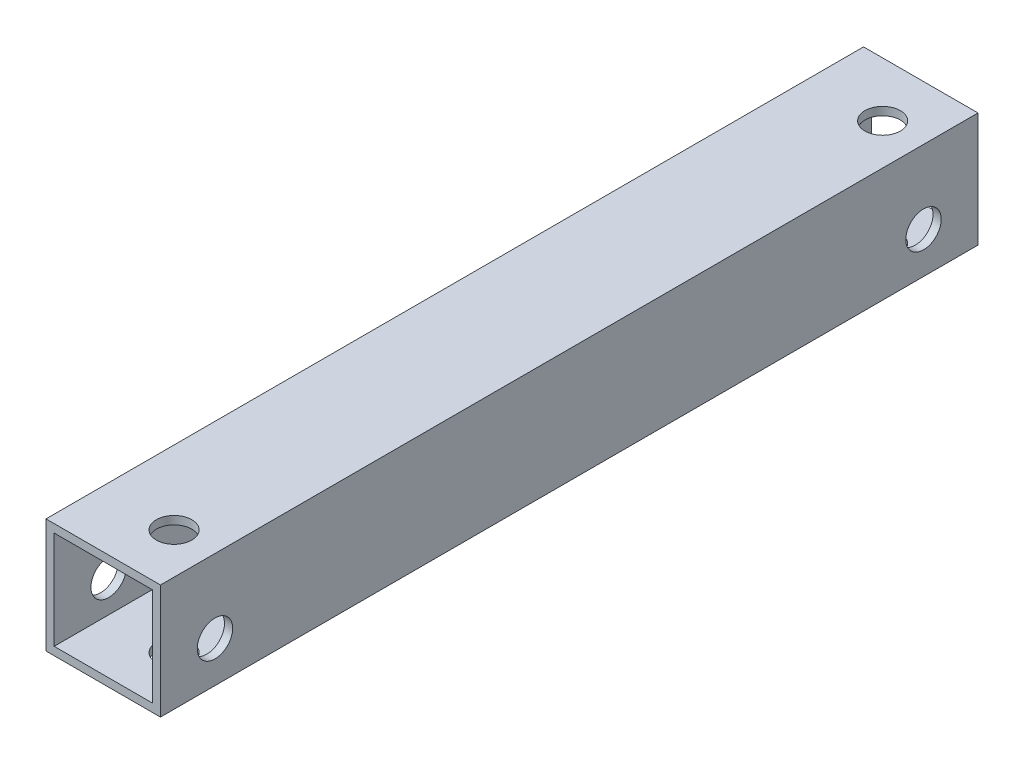
SolidWorks part; units mm, degrees
ref_plane "Alzado" through (0, 0, 0) normal (0, 0, 1) x (1, 0, 0)
ref_plane "Planta" through (0, 0, 0) normal (0, 1, 0) x (1, 0, 0)
ref_plane "Vista lateral" through (0, 0, 0) normal (1, 0, 0) x (0, 0, -1)
sketch "Croquis1" plane through (0, 0, 0) normal (0, 0, 1) x (1, 0, 0)
  line L0 (-18, 18) -> (18, 18)
  line L1 (-21, -21) -> (21, -21)
  line L2 (-21, -21) -> (-21, 21)
  line L3 (-21, 21) -> (21, 21)
  line L4 (21, -21) -> (21, 21)
  line L5 (-21, -21) -> (21, 21) construction
  line L6 (-21, 21) -> (21, -21) construction
  line L7 (18, -18) -> (18, 18)
  line L8 (-18, -18) -> (18, -18)
  line L9 (-18, -18) -> (-18, 18)
  point P0 (0, 0)
  dimension "D1" = 42
  dimension "D2" = 42
  dimension "D3" = 3
extrude "Saliente-Extruir1" add sketch "Croquis1" along normal mid plane 300
sketch "Croquis2" plane through (21, 0, 0) normal (1, 0, 0) x (0, 0, -1)
  line L0 (-150, -6) -> (150, -6) construction
  line L1 (-150, -21) -> (-150, 21) construction
  line L2 (150, -21) -> (150, 21) construction
  line L3 (-150, -21) -> (150, -21) construction
  line L4 (-130, 21) -> (-130, -21) construction
  line L5 (-150, 21) -> (150, 21) construction
  line L6 (0, 21) -> (0, -21) construction
  circle A0 centre (-130, -6) radius 6.5
  circle A1 centre (130, -6) radius 6.5
  dimension "D3" = 13
  dimension "D1" = 15
  dimension "D2" = 20
extrude "Cortar-Extruir1" cut sketch "Croquis2" against normal blind 300
sketch "Croquis3" plane through (0, -21, 0) normal (0, -1, 0) x (1, 0, 0)
  line L0 (6, -150) -> (6, 150) construction
  line L1 (-21, -150) -> (21, -150) construction
  line L2 (-21, 150) -> (21, 150) construction
  line L3 (21, 150) -> (21, -150) construction
  line L4 (-19.7, 0) -> (31.2347, 0) construction
  circle A0 centre (6, -130) radius 6.5
  circle A1 centre (6, 130) radius 6.5
  dimension "D3" = 13
  dimension "D1" = 15
  dimension "D2" = 20
extrude "Cortar-Extruir2" cut sketch "Croquis3" against normal through all
